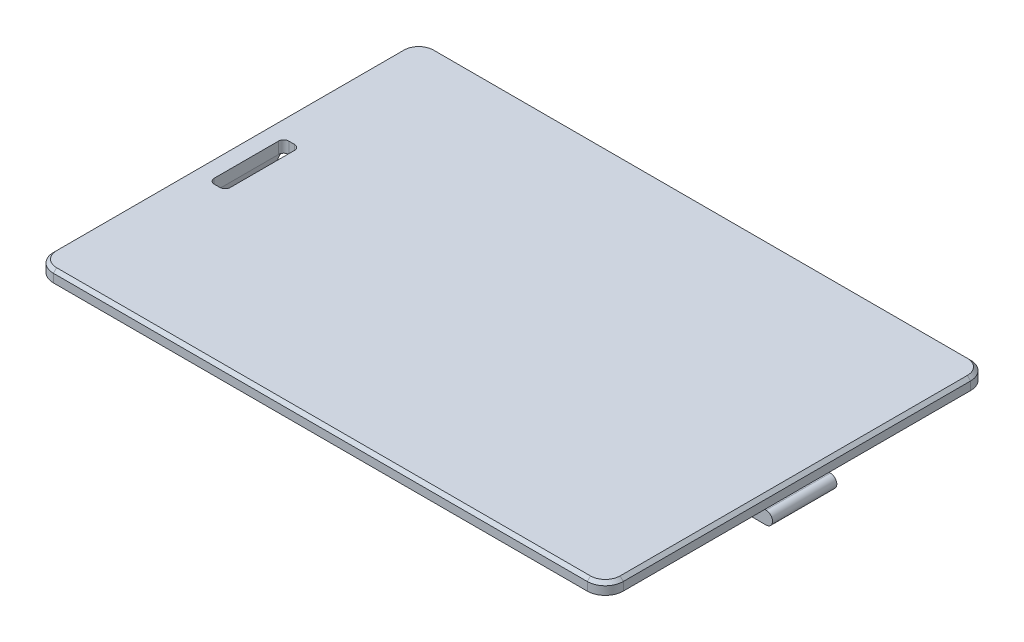
SolidWorks part; units mm, degrees
ref_plane "Ebene vorne" through (0, 0, 0) normal (0, 0, 1) x (1, 0, 0)
ref_plane "Ebene oben" through (0, 0, 0) normal (0, 1, 0) x (1, 0, 0)
ref_plane "Ebene rechts" through (0, 0, 0) normal (1, 0, 0) x (0, 0, -1)
sketch "Skizze1" plane through (0, 0, 0) normal (0, 1, 0) x (1, 0, 0)
  line L1 (-44.3, 29.8) -> (44.3, 29.8)
  line L2 (-44.3, 29.8) -> (-44.3, -29.8)
  line L3 (-44.3, -29.8) -> (44.3, -29.8)
  line L4 (44.3, 29.8) -> (44.3, -29.8)
  line L5 (-44.3, 29.8) -> (44.3, -29.8) construction
  line L6 (-44.3, -29.8) -> (44.3, 29.8) construction
  point P0 (0, 0)
  dimension "D1" = 88.6
  dimension "D2" = 59.6
extrude "Aufsatz-Linear austragen1" add sketch "Skizze1" along normal blind 1.8
sketch "Skizze2" plane through (0, 1.8, 0) normal (0, 1, 0) x (1, 0, 0)
  line L0 (-44.3, 29.8) -> (-44.3, -29.8) construction
  line L1 (44.3, 29.8) -> (-44.3, 29.8) construction
  line L2 (-44.3, -29.8) -> (44.3, -29.8) construction
  line L3 (44.3, -29.8) -> (44.3, 29.8) construction
  line L8 (44.3, -29.8) -> (44.3, 29.8)
  line L9 (44.3, 29.8) -> (-44.3, 29.8)
  line L10 (-44.3, 29.8) -> (-44.3, -29.8)
  line L11 (-44.3, -29.8) -> (44.3, -29.8)
  line L12 (44.3, -29.8) -> (44.3, 29.8)
  line L13 (44.3, 29.8) -> (-44.3, 29.8)
  line L14 (-44.3, 29.8) -> (-44.3, -29.8)
  line L15 (-44.3, -29.8) -> (44.3, -29.8)
  arc A0 (-44.3, 27) -> (-41.5, 29.8) centre (-41.5, 27) cw
  arc A1 (-44.3, -27) -> (-41.5, -29.8) centre (-41.5, -27) ccw
  arc A2 (41.5, 29.8) -> (44.3, 27) centre (41.5, 27) cw
  arc A3 (41.5, -29.8) -> (44.3, -27) centre (41.5, -27) ccw
  point P3 (0, 0)
  point P8 (0, 0)
  point P12 (0, 0)
  line M5 (44.3, -29.8) -> (44.3, 29.8)
  line M6 (44.3, 29.8) -> (-44.3, 29.8)
  line M7 (-44.3, 29.8) -> (-44.3, -29.8)
  line M8 (-44.3, -29.8) -> (44.3, -29.8)
  dimension "D3" = 0
  dimension "D1" = 54
  dimension "D2" = 83
extrude "Schnitt-Linear austragen1" cut sketch "Skizze2" against normal through all contours A1 M7 M8 | A3 M8 M5 | A2 L12 M6 | A0 L13 M7 region at (43.6746, 1.8, 29.1746) region at (43.6746, 1.8, -29.1746) region at (-43.6746, 1.8, 29.1746) region at (-43.6746, 1.8, -29.1746)
chamfer "Fase1" distance 0.5 angle 45 8 edges at (-44.3, 1.8, 0) (-43.4799, 1.8, 28.9799) (-43.4799, 1.8, -28.9799) (0, 1.8, 29.8) (0, 1.8, -29.8) (43.4799, 1.8, 28.9799) (43.4799, 1.8, -28.9799) (44.3, 1.8, 0)
sketch "Skizze3" plane through (0, 0, 0) normal (0, 0, 1) x (1, 0, 0)
  line L0 (44.5, 0) -> (40.5, 0)
  line L1 (-41.5, 0) -> (41.5, 0) construction
  line L2 (44.3, 0) -> (44.3, 1.3) construction
  line L3 (44.5, -2) -> (42.5, -2)
  arc A0 (44.5, 0) -> (44.5, -2) centre (44.5, -1) cw
  arc A1 (40.5, 0) -> (41.5, -1) centre (40.5, -1) cw
  arc A2 (41.5, -1) -> (42.5, -2) centre (42.5, -1) ccw
  dimension "D2" = 1
  dimension "D5" = 1
  dimension "D6" = 1
  dimension "D1" = 0.2
  dimension "D3" = 2
  dimension "D4" = 2
extrude "Aufsatz-Linear austragen2" add sketch "Skizze3" along normal mid plane 10
sketch "Skizze4" plane through (0, 0, 0) normal (0, 0, 1) x (1, 0, 0)
  line L0 (-44.3, 0) -> (-44.3, -8)
  line L1 (-44.3, -8) -> (-47, -8)
  line L2 (-47, -8) -> (-47, -9.5)
  line L3 (-47, -9.5) -> (-45, -11.5)
  line L4 (-44.3, 0) -> (-41.3, 0)
  line L5 (-41.5, 0) -> (41.5, 0) construction
  line L6 (-41.3, 0) -> (-43.2396, -11)
  arc A0 (-45, -11.5) -> (-43.2396, -11) centre (-44.241, -10.8234) ccw
  dimension "D1" = 8
  dimension "D2" = 2.7
  dimension "D3" = 1.5
  dimension "D4" = 45
  dimension "D5" = 2
  dimension "D6" = 3
  dimension "D7" = 10
  dimension "D8" = 11
extrude "Aufsatz-Linear austragen3" add sketch "Skizze4" along normal mid plane 10
fillet "Verrundung1" radius 0.8 2 edges at (-42.8, 0, -5) (-42.8, 0, 5)
sketch "Skizze5" plane through (0, 0, 0) normal (0, -1, 0) x (1, 0, 0)
  line L0 (-41.3, 0) -> (-40.05, 0) construction
  line L1 (-38.8, -5.8) -> (-41.3, -5.8)
  line L2 (-38.8, -5.8) -> (-38.8, 5.8)
  line L3 (-38.8, 5.8) -> (-41.3, 5.8)
  line L4 (-41.3, -5.8) -> (-41.3, 5.8)
  line L5 (-38.8, -5.8) -> (-41.3, 5.8) construction
  line L6 (-38.8, 5.8) -> (-41.3, -5.8) construction
  line L7 (-41.3, 5.8) -> (-41.3, -5.8) construction
  point P0 (-40.05, 0)
  dimension "D1" = 2.5
  dimension "D2" = 11.6
extrude "Schnitt-Linear austragen2" cut sketch "Skizze5" against normal through all
fillet "Verrundung2" radius 0.8 4 edges at (-38.8, 0.9, -5.8) (-41.3, 0.9, -5.8) (-38.8, 0.9, 5.8) (-41.3, 0.9, 5.8)
